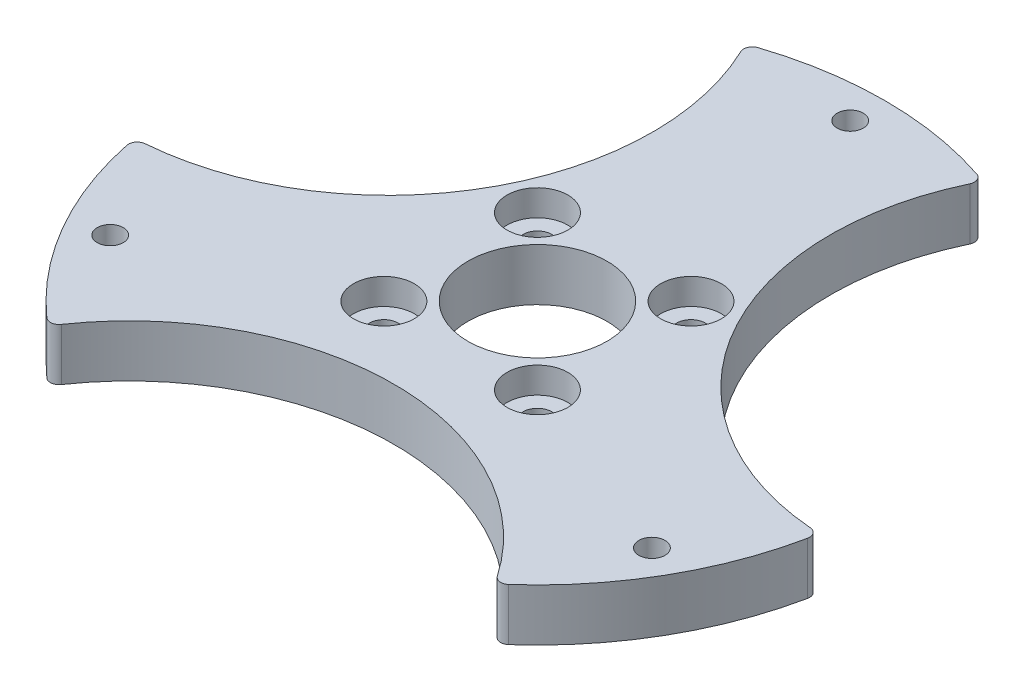
SolidWorks part; units mm, degrees
ref_plane "Front Plane" through (0, 0, 0) normal (0, 0, 1) x (1, 0, 0)
ref_plane "Top Plane" through (0, 0, 0) normal (0, 1, 0) x (1, 0, 0)
ref_plane "Right Plane" through (0, 0, 0) normal (1, 0, 0) x (0, 0, -1)
sketch "Sketch1" plane through (0, 0, 0) normal (0, 1, 0) x (1, 0, 0)
  circle A0 centre (0, 0) radius 40
  dimension "D1" = 80
extrude "Boss-Extrude1" add sketch "Sketch1" along normal blind 6
sketch "Sketch2" plane through (0, 0, 0) normal (0, 1, 0) x (1, 0, 0)
  line L0 (-13.6808, 37.5877) -> (0, 0) construction
  line L1 (0, 0) -> (13.6808, 37.5877) construction
  line L2 (0, -1000) -> (0, 49000) construction
  line L3 (-13.6808, 37.5877) -> (-10.9446, 30.0702)
  line L4 (13.6808, 37.5877) -> (10.9446, 30.0702)
  line L5 (39.3923, -6.9459) -> (31.5138, -5.5567)
  line L6 (25.7115, -30.6418) -> (20.5692, -24.5134)
  line L7 (-25.7115, -30.6418) -> (-20.5692, -24.5134)
  line L8 (-39.3923, -6.9459) -> (-31.5138, -5.5567)
  circle A0 centre (0, 0) radius 40 construction
  arc A1 (-13.6808, 37.5877) -> (13.6808, 37.5877) centre (0, 0) cw
  arc A2 (-10.9446, 30.0702) -> (10.9446, 30.0702) centre (0, 0) cw
  arc A3 (39.3923, -6.9459) -> (25.7115, -30.6418) centre (0, 0) cw
  arc A4 (31.5138, -5.5567) -> (20.5692, -24.5134) centre (0, 0) cw
  arc A5 (-25.7115, -30.6418) -> (-39.3923, -6.9459) centre (0, 0) cw
  arc A6 (-20.5692, -24.5134) -> (-31.5138, -5.5567) centre (0, 0) cw
  point P21 (0, 0)
  dimension "D1" = 20
  dimension "D2" = 20
  dimension "D3" = 8
  dimension "D4" = 3
sketch "Sketch3" plane through (0, 6, 0) normal (0, 1, 0) x (1, 0, 0)
  circle A0 centre (40.6986, 23.4973) radius 30.4713
extrude "Cut-Extrude1" cut sketch "Sketch3" against normal through all
sketch "Sketch5" plane through (0, 6, 0) normal (0, 1, 0) x (1, 0, 0)
  circle A0 centre (0, 36) radius 1.5
  dimension "D2" = 3
  dimension "D1" = 36
extrude "Cut-Extrude2" cut sketch "Sketch5" against normal through all
pattern_circular "CirPattern1" count 3 over 360 about axis through (0, 6, 0) along (0, -1, 0) of "Cut-Extrude1", "Cut-Extrude2" reverse direction yes
sketch "Sketch6" plane through (0, 6, 0) normal (0, 1, 0) x (1, 0, 0)
  line L1 (-8.8388, -8.8388) -> (8.8388, -8.8388) construction
  line L2 (-8.8388, -8.8388) -> (-8.8388, 8.8388) construction
  line L3 (-8.8388, 8.8388) -> (8.8388, 8.8388) construction
  line L4 (8.8388, -8.8388) -> (8.8388, 8.8388) construction
  line L5 (-8.8388, -8.8388) -> (8.8388, 8.8388) construction
  line L6 (-8.8388, 8.8388) -> (8.8388, -8.8388) construction
  circle A0 centre (8.8388, 8.8388) radius 1.65
  circle A1 centre (-8.8388, 8.8388) radius 1.65
  circle A2 centre (-8.8388, -8.8388) radius 1.65
  circle A3 centre (8.8388, -8.8388) radius 1.65
  point P0 (0, 0)
  dimension "D1" = 3.3
  dimension "D2" = 12.5
extrude "Cut-Extrude3" cut sketch "Sketch6" against normal through all
sketch "Sketch7" plane through (0, 6, 0) normal (0, 1, 0) x (1, 0, 0)
  circle A0 centre (0, 0) radius 8
  dimension "D1" = 16
extrude "Cut-Extrude4" cut sketch "Sketch7" against normal through all
fillet "Fillet1" radius 1 6 edges at (-39.3923, 3, 6.9459) (-13.6808, 3, -37.5877) (25.7115, 3, 30.6418) (-25.7115, 3, 30.6418) (39.3923, 3, 6.9459) (13.6808, 3, -37.5877)
sketch "Sketch8" plane through (0, 6, 0) normal (0, -1, 0) x (1, 0, 0)
  circle A0 centre (8.8388, 8.8388) radius 3.5
  circle A1 centre (8.8388, -8.8388) radius 3.5
  circle A2 centre (-8.8388, 8.8388) radius 3.5
  circle A3 centre (-8.8388, -8.8388) radius 3.5
  dimension "D1" = 7
extrude "Cut-Extrude5" cut sketch "Sketch8" along normal blind 3
